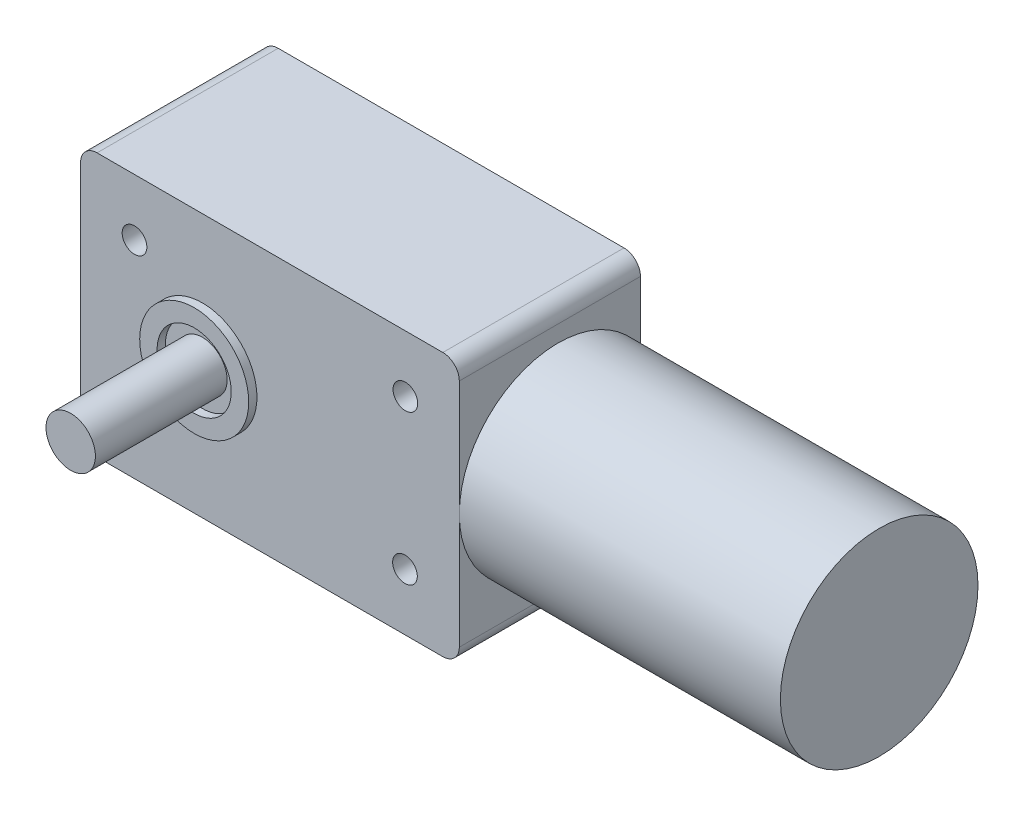
SolidWorks part; units mm, degrees
ref_plane "Front Plane" through (0, 0, 0) normal (0, 0, 1) x (1, 0, 0)
ref_plane "Top Plane" through (0, 0, 0) normal (0, 1, 0) x (1, 0, 0)
ref_plane "Right Plane" through (0, 0, 0) normal (1, 0, 0) x (0, 0, -1)
sketch "Sketch1" plane through (0, 0, 0) normal (0, 0, 1) x (1, 0, 0)
  line L1 (-21, -16) -> (21, -16)
  line L2 (-23, -14) -> (-23, 14)
  line L3 (-21, 16) -> (21, 16)
  line L4 (23, -14) -> (23, 14)
  line L5 (-23, -16) -> (23, 16) construction
  line L6 (-23, 16) -> (23, -16) construction
  arc A0 (-21, -16) -> (-23, -14) centre (-21, -14) cw
  arc A1 (21, -16) -> (23, -14) centre (21, -14) ccw
  arc A2 (21, 16) -> (23, 14) centre (21, 14) cw
  arc A3 (-23, 14) -> (-21, 16) centre (-21, 14) cw
  point P0 (0, 0)
  dimension "D3" = 2
  dimension "D1" = 46
  dimension "D2" = 32
extrude "Boss-Extrude1" add sketch "Sketch1" along normal blind 22
sketch "Sketch2" plane through (0, 0, 22) normal (0, 0, 1) x (1, 0, 0)
  line L0 (-23, 14) -> (-23, -14) construction
  line L1 (21, 16) -> (-21, 16) construction
  line L2 (-23, 0) -> (23, 0) construction
  line L3 (23, -14) -> (23, 14) construction
  circle A0 centre (-16.45, 9.1) radius 1.5
  circle A1 centre (16.45, 9.1) radius 1.5
  circle A2 centre (16.4, -9.0999) radius 1.5
  circle A3 centre (-16.5, -9.0999) radius 1.5
  dimension "D1" = 3
  dimension "D2" = 6.55
  dimension "D3" = 6.9
  dimension "D4" = 2
  dimension "D6" = 18.2
  dimension "D7" = 32.9
  dimension "D8" = 6.5
  dimension "D5" = 2
extrude "Cut-Extrude1" cut sketch "Sketch2" against normal blind 3
sketch "Sketch3" plane through (0, 0, 22) normal (0, 0, 1) x (1, 0, 0)
  line L3 (-23, 14) -> (-23, -14) construction
  circle A0 centre (-8.2, 0) radius 3
  circle A2 centre (-8.2, 0) radius 4.5
  circle A3 centre (-8.2, 0) radius 6.62
  dimension "D1" = 6
  dimension "D2" = 9
  dimension "D4" = 13.24
  dimension "D3" = 14.8
extrude "Boss-Extrude2" add sketch "Sketch3" along normal blind 1 contours A3 A2 region at (-14.6328, 0, 22)
extrude "Boss-Extrude3" add sketch "Sketch3<3>" along normal blind 16 contours A0
sketch "Sketch3<3>" plane through (0, 0, 22) normal (0, 0, 1) x (1, 0, 0) same geometry as "Sketch3"
sketch "Sketch4" plane through (23, 0, 0) normal (1, 0, 0) x (0, 0, -1)
  line L0 (-22, -14) -> (-22, 14) construction
  circle A0 centre (-10, 0) radius 12
  point P4 (0, 0)
  dimension "D1" = 24
extrude "Boss-Extrude4" add sketch "Sketch4" along normal blind 39
